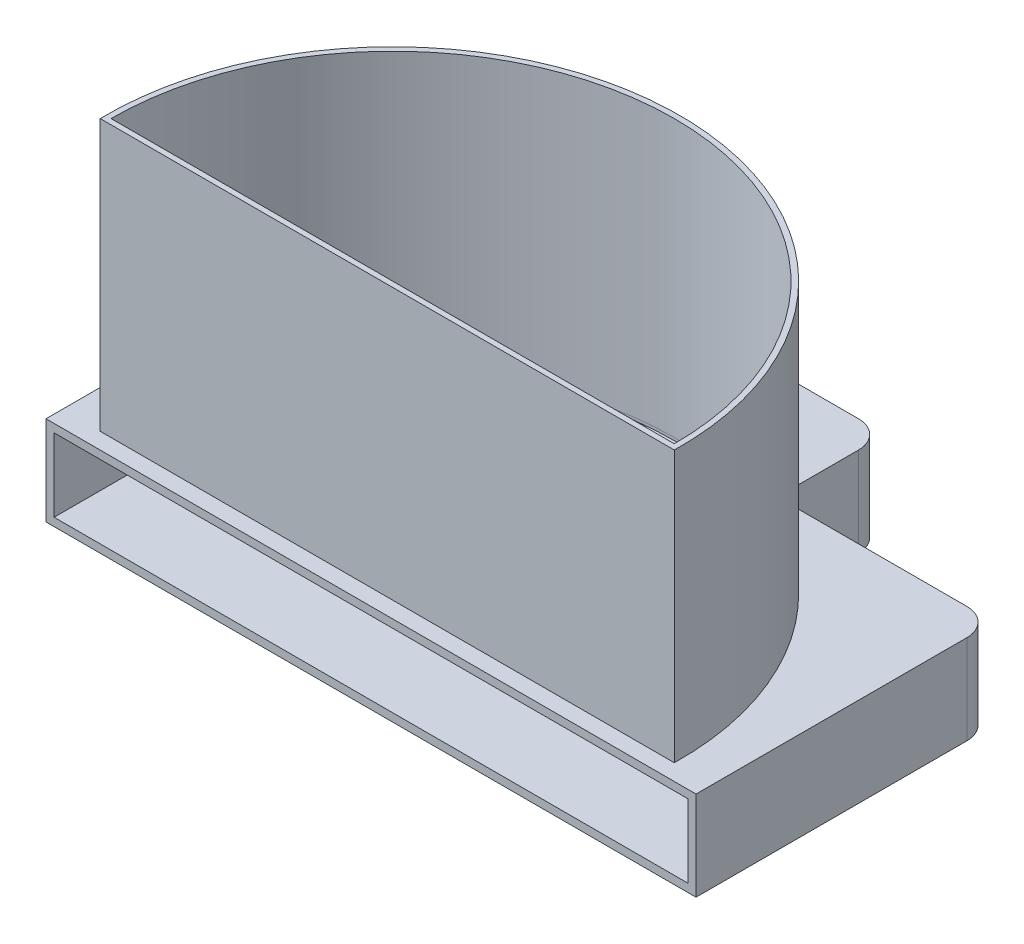
SolidWorks part; units mm, degrees
ref_plane "前视基准面" through (0, 0, 0) normal (0, 0, 1) x (1, 0, 0)
ref_plane "上视基准面" through (0, 0, 0) normal (0, 1, 0) x (1, 0, 0)
ref_plane "右视基准面" through (0, 0, 0) normal (1, 0, 0) x (0, 0, -1)
other "Configuration Table"
sketch "草图1" plane through (0, 0, 0) normal (0, 1, 0) x (1, 0, 0)
  line L0 (-120, 35) -> (-40, 35)
  line L1 (-40, 75) -> (40, 75)
  line L2 (-120, 35) -> (-120, -75)
  line L3 (-120, -75) -> (120, -75)
  line L4 (120, 35) -> (120, -75)
  line L5 (-56, 35) -> (120, -75) construction
  line L6 (-120, -75) -> (56, 35) construction
  line L7 (-40, 35) -> (-40, 75)
  line L9 (40, 75) -> (40, 35)
  line L10 (40, 35) -> (120, 35)
  point P0 (0, 0)
  point P4 (0, 0)
  point P5 (0, 35)
  dimension "D1" = 240
  dimension "D3" = 110
  dimension "D4" = 80
extrude "凸台-拉伸2" add sketch "草图1" along normal blind 33
shell "抽壳5" thickness 3 removed face at (0, 16.5, 75) removed face at (0, 33, -17.5)
fillet "圆角2" radius 10 4 edges at (40, 16.5, -75) (-40, 16.5, -75) (120, 16.5, -35) (-120, 16.5, -35)
ref_plane "基准面1" through (0, 30, 0) normal (0, 1, 0) x (1, 0, 0)
sketch "草图2" plane through (0, 30, 0) normal (0, 1, 0) x (1, 0, 0)
  line L0 (-117, -75) -> (117, -75)
  line L1 (117, -75) -> (117, 32)
  line L2 (117, 32) -> (37, 32)
  line L3 (37, 32) -> (37, 72)
  line L4 (37, 72) -> (-37, 72)
  line L5 (-37, 72) -> (-37, 32)
  line L6 (-37, 32) -> (-117.0711, 32.0711)
  line L7 (-117.0711, 32.0711) -> (-117, -75)
  arc A0 (-110, 35) -> (-120, 25) centre (-110, 25) ccw construction
extrude "凸台-拉伸3" add sketch "草图2" along normal blind 3
sketch "草图3" plane through (0, 30, 0) normal (0, 1, 0) x (1, 0, 0)
  line L1 (-104, -67) -> (104, -67)
  arc A1 (-104, -67) -> (104, -67) centre (0, -67) cw
  point P6 (-104, -67)
  point P7 (104, -67)
  point P9 (0, 37)
extrude "切除-拉伸2" cut sketch "草图3" along normal blind 3
ref_plane "基准面2" through (0, 33, 0) normal (0, 1, 0) x (1, 0, 0)
sketch "草图5" plane through (0, 33, 0) normal (0, 1, 0) x (1, 0, 0)
  line L0 (-104, -67) -> (104, -67)
  arc A0 (-104, -67) -> (104, -67) centre (0, -67) cw
extrude "凸台-拉伸7" add sketch "草图5" along normal blind 100 separate body
shell "抽壳8" thickness 2 removed face at (0, 133, 15) outward yes
sketch "草图7" plane through (0, 30, 0) normal (0, 1, 0) x (1, 0, 0)
  line L0 (-104, -67) -> (104, -67)
  arc A0 (-104, -67) -> (104, -67) centre (0, -67) cw
extrude "切除-拉伸3" cut sketch "草图7" against normal blind 3 and the other way blind 3
